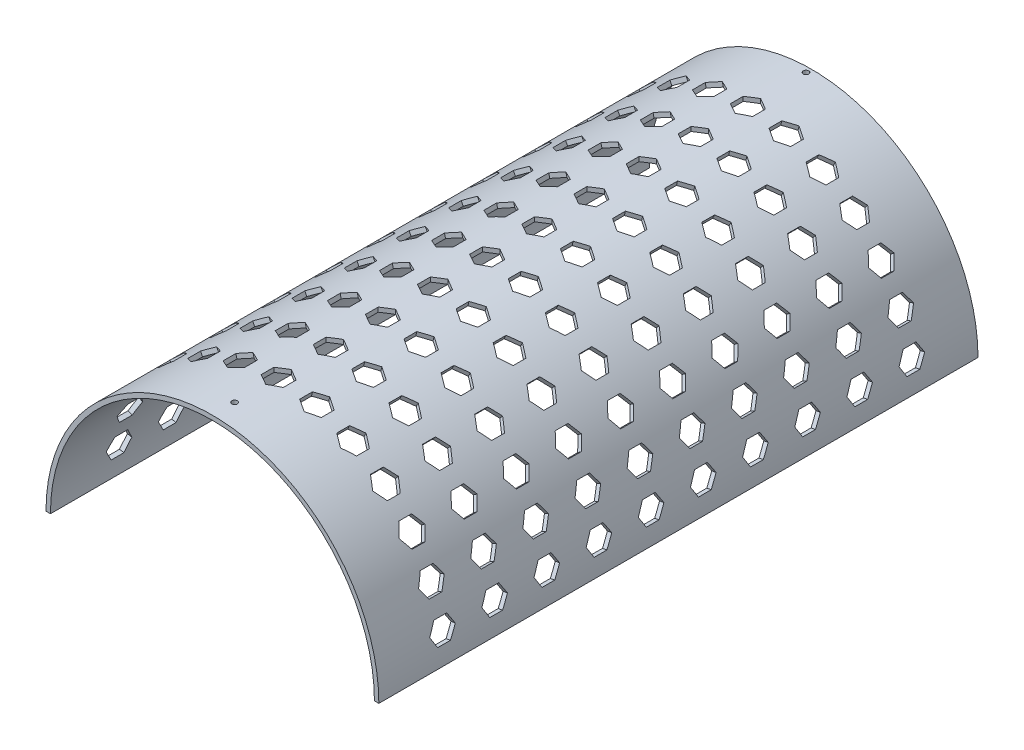
SolidWorks part; units mm, degrees
ref_plane "Front Plane" through (0, 0, 0) normal (0, 0, 1) x (1, 0, 0)
ref_plane "Top Plane" through (0, 0, 0) normal (0, 1, 0) x (1, 0, 0)
ref_plane "Right Plane" through (0, 0, 0) normal (1, 0, 0) x (0, 0, -1)
sketch "Sketch1" plane through (0, 0, 0) normal (0, 0, 1) x (1, 0, 0)
  line L0 (-75, 0) -> (-73, 0)
  line L1 (-73, 0) -> (73, 0) construction
  line L2 (73, 0) -> (75, 0)
  arc A0 (75, 0) -> (-75, 0) centre (0, 0) ccw
  arc A1 (73, 0) -> (-73, 0) centre (0, 0) ccw
  arc A2 (-75, 0) -> (75, 0) centre (0, 0) ccw construction
  circle A3 centre (0, 0) radius 75 construction
  arc A4 (-73, 0) -> (73, 0) centre (0, 0) ccw construction
  circle A5 centre (0, 0) radius 73 construction
  dimension "D1" = 150
  dimension "D2" = 2
extrude "Boss-Extrude1" add sketch "Sketch1" along normal blind 270
sketch "Sketch4" plane through (0, 0, 0) normal (0, 1, 0) x (1, 0, 0)
  line L0 (-75, -270) -> (75, -270) construction
  line L1 (75, 0) -> (-75, 0) construction
  circle A0 centre (0, -2.5) radius 1.25
  circle A1 centre (0, -260) radius 1.25
  dimension "D1" = 2.5
  dimension "D3" = 2.5
  dimension "D2" = 10
  dimension "D4" = 2.5
extrude "Cut-Extrude2" cut sketch "Sketch4" along normal up to surface (75 mm away) up to face at (0, 37.5, 135)
sketch "Sketch2" plane through (0, 0, 0) normal (0, 1, 0) x (1, 0, 0)
  line L0 (0, 0) -> (0, -28.6927) construction
  line L1 (5, -31.5794) -> (5, -25.8059)
  line L2 (5, -25.8059) -> (0, -22.9192)
  line L3 (0, -22.9192) -> (-5, -25.8059)
  line L4 (-5, -25.8059) -> (-5, -31.5794)
  line L5 (-5, -31.5794) -> (0, -34.4662)
  line L6 (0, -34.4662) -> (5, -31.5794)
  circle A1 centre (0, -28.6927) radius 5 construction
  dimension "D1" = 10
extrude "Cut-Extrude3" cut sketch "Sketch2" along normal up to surface (74.8331 mm away) up to face at (0, 37.5, 135)
pattern_circular "CirPattern1" count 7 every 13.333 about axis through (0, 0, 270) along (0, 0, -1) of "Cut-Extrude3" reverse direction yes other way count 7
pattern_linear "LPattern1" count 10 spacing 23.5 along (0, 0, 1) of "CirPattern1", "Cut-Extrude3"
